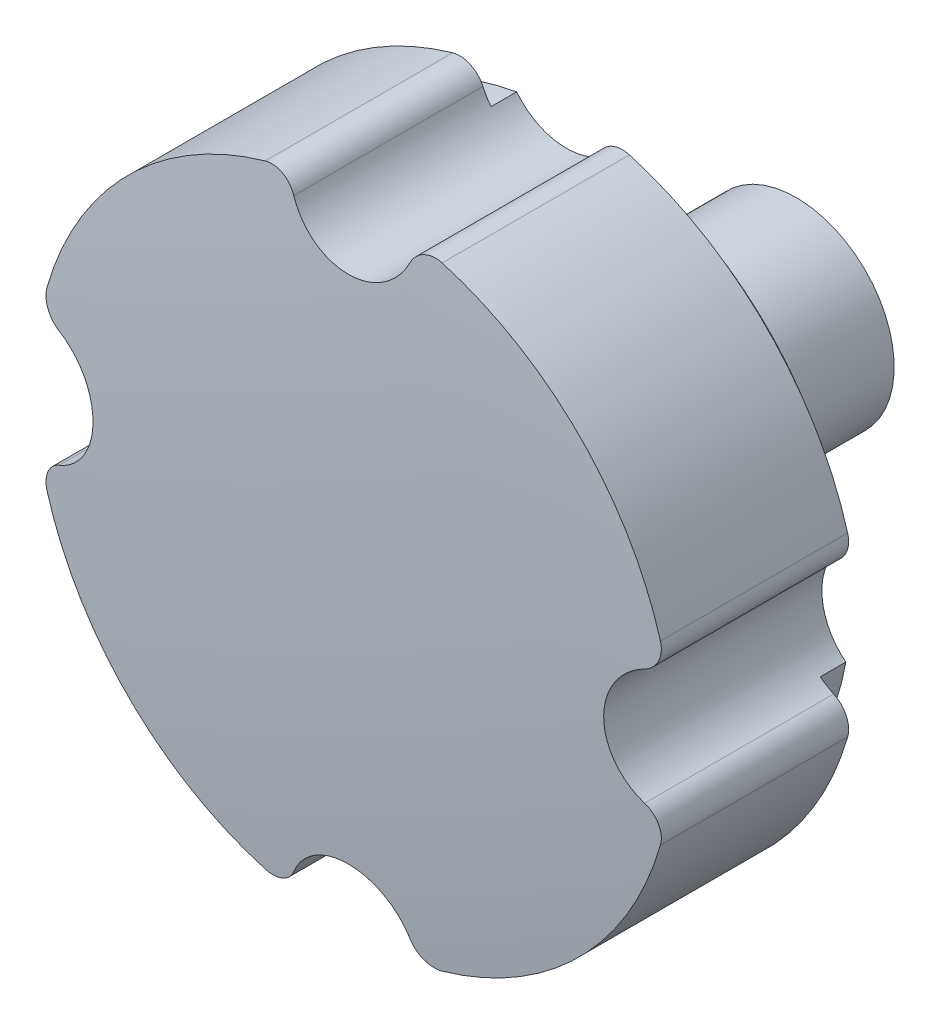
SolidWorks part; units mm, degrees
ref_plane "Front Plane" through (0, 0, 0) normal (0, 0, 1) x (1, 0, 0)
ref_plane "Top Plane" through (0, 0, 0) normal (0, 1, 0) x (1, 0, 0)
ref_plane "Right Plane" through (0, 0, 0) normal (1, 0, 0) x (0, 0, -1)
sketch "Sketch1" plane through (0, 0, 0) normal (0, 1, 0) x (1, 0, 0)
  line L0 (0, 358.8435) -> (0, -36.4755) construction
  line L1 (0, 23.7617) -> (0, 0)
  line L2 (-37.5, 1.7617) -> (-37.5, 23.7617)
  line L3 (-37.5, 23.7617) -> (-33.34, 23.7617)
  line L4 (-33.34, 23.7617) -> (-33.34, 26.7617)
  line L5 (-33.34, 26.7617) -> (-11.5, 26.7617)
  line L6 (-11.5, 26.7617) -> (-11.5, 53.7617)
  line L7 (-11.5, 53.7617) -> (-6, 53.7617)
  line L8 (-6, 53.7617) -> (-6, 23.7617)
  line L9 (-6, 23.7617) -> (0, 23.7617)
  arc A1 (-37.5, 1.7617) -> (0, 0) centre (0, 400) ccw
  dimension "D9" = 800
  dimension "D1" = 30
  dimension "D2" = 22
  dimension "D3" = 3
  dimension "D4" = 75
  dimension "D5" = 23
  dimension "D6" = 12
  dimension "D7" = 66.68
  dimension "D8" = 30
revolve "Revolve1" add sketch "Sketch1" angle 360 about L0
sketch "Sketch2" plane through (0, 0, 0) normal (0, 0, 1) x (1, 0, 0)
  circle A0 centre (0, 0) radius 37.5 construction
  circle A1 centre (0, 37.5) radius 7.5
  circle A2 centre (0, 0) radius 37.5 construction
  circle A3 centre (37.5, 0) radius 7.5
  circle A4 centre (0, 0) radius 37.5 construction
  circle A5 centre (0, -37.5) radius 7.5
  circle A6 centre (0, 0) radius 37.5 construction
  circle A7 centre (-37.5, 0) radius 7.5
  point P17 (0, 0)
  dimension "D1" = 75
  dimension "D2" = 15
  dimension "D3" = 4
extrude "Cut-Extrude1" cut sketch "Sketch2" against normal up to next
ref_plane "Plane1" through (0, 0, -23.7617) normal (0, 0, -1) x (-1, 0, 0)
sketch "Sketch3" plane through (0, 0, -23.7617) normal (0, 0, -1) x (-1, 0, 0)
  line L0 (0, 0) -> (-57.745, 57.745) construction
  line L1 (0, 0) -> (-62.0039, 0) construction
  dimension "D1" = 45
fillet "Fillet1" radius 3 8 edges at (-36.75, 7.4624, -12.7617) (-36.75, -7.4624, -12.7617) (-7.4624, -36.75, -12.7617) (7.4624, -36.75, -12.7617) (36.75, -7.4624, -12.7617) (36.75, 7.4624, -12.7617) (7.4624, 36.75, -12.7617) (-7.4624, 36.75, -12.7617)
sketch "Sketch4" plane through (0, 0, 0) normal (0, 1, 0) x (1, 0, 0)
  line L0 (0, 68.9802) -> (0, -14.4472) construction
sketch "Sketch5" plane through (0, 0, 0) normal (0, 0, 1) x (1, 0, 0)
  line L0 (0, 0) -> (-33.6671, 33.6671) construction
